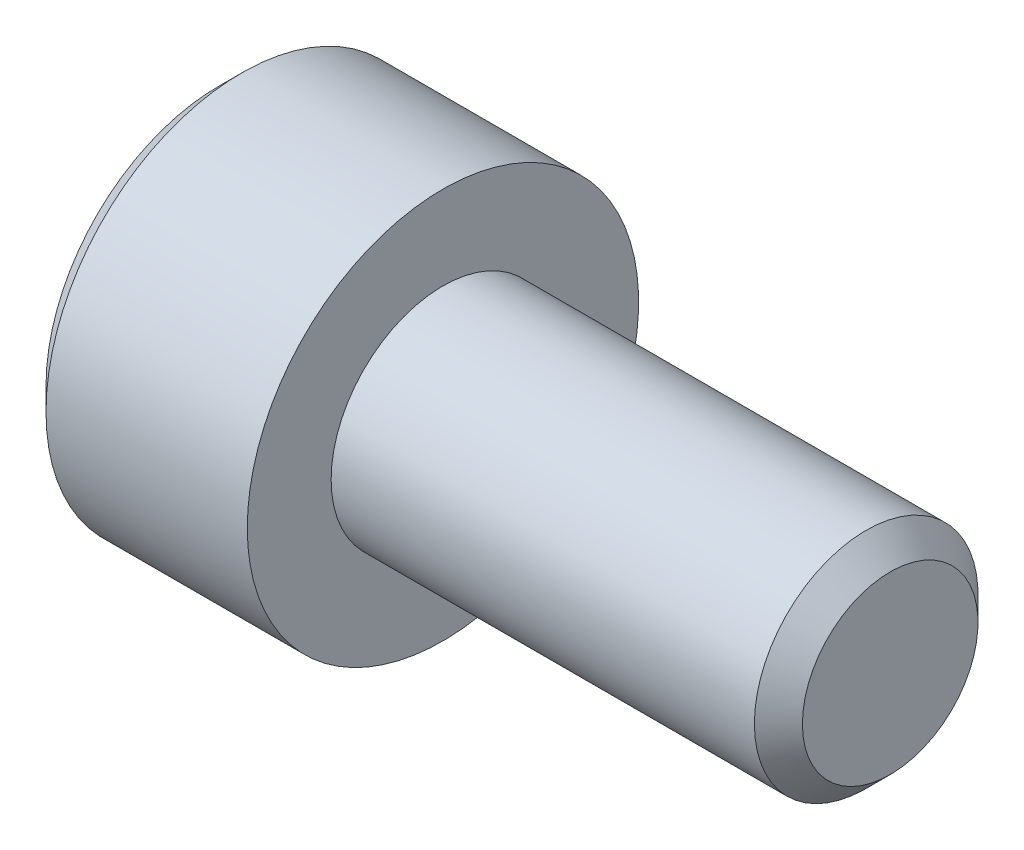
SolidWorks part; units mm, degrees
ref_plane "Front Plane" through (0, 0, 0) normal (0, 0, 1) x (1, 0, 0)
ref_plane "Top Plane" through (0, 0, 0) normal (0, 1, 0) x (1, 0, 0)
ref_plane "Right Plane" through (0, 0, 0) normal (1, 0, 0) x (0, 0, -1)
ref_plane "Plane1" through (1, 0, 0) normal (1, 0, 0) x (0, 0, -1)
ref_axis "Axis_X" through (-4.6, 0, 0) along (1, 0, 0)
ref_axis "Axis_Y" through (0, 3.85, 0) along (0, -1, 0)
ref_axis "Axis_Z" through (0, 0, -3.85) along (0, 0, 1)
sketch "Sketch1" plane through (0, 0, 0) normal (0, 0, 1) x (1, 0, 0)
  line L0 (-4, 0) -> (8, 0)
  line L1 (8, 0) -> (8, -1.5705)
  line L2 (8, -1.5705) -> (7.5705, -2)
  line L3 (7.5705, -2) -> (0, -2)
  line L4 (0, -2) -> (0, -3.5)
  line L5 (0, -3.5) -> (-3.6, -3.5)
  line L6 (-3.6, -3.5) -> (-4, -3.1)
  line L7 (-4, -3.1) -> (-4, 0)
  line L8 (0, 0) -> (-4, 0) construction
  line L9 (8, 1.5705) -> (7.5705, 2) construction
  line L10 (-4, 3.1) -> (-3.6, 3.5) construction
  point P16 (7.3, -2)
  dimension "A" = 7
  dimension "E" = 4
  dimension "MSM_1" = 3.141
  dimension "MSM_2" = 45
  dimension "MSM_3" = 0.4
  dimension "L" = 8
  dimension "Pitch_1" = 0.7
revolve "Revolve1" add sketch "Sketch1" angle 360 about axis through (-4.6, 0, 0) along (1, 0, 0)
sketch "Sketch2" plane through (-4, 0, 0) normal (-1, 0, 0) x (0, 0, 1)
  line L1 (0, 1.7321) -> (-1.5, 0.866)
  line L2 (-1.5, 0.866) -> (-1.5, -0.866)
  line L3 (-1.5, -0.866) -> (0, -1.7321)
  line L4 (0, -1.7321) -> (1.5, -0.866)
  line L5 (1.5, -0.866) -> (1.5, 0.866)
  line L6 (1.5, 0.866) -> (0, 1.7321)
  circle A0 centre (0, 0) radius 1.5 construction
  dimension "B" = 3
extrude "Cut-Extrude1" cut sketch "Sketch2" against normal blind 2
ref_plane "Dim. B_s" through (8, 0, 0) normal (1, 0, 0) x (0, 0, -1)
sketch "Sketch3" plane through (0, 0, 0) normal (0, 0, 1) x (1, 0, 0)
  line L0 (0, 0) -> (8, 0) construction
  line L1 (8, -1.3128) -> (8, 1.3128) construction
  line L3 (7.99, 2) -> (8, 2)
  line L5 (7.99, 2) -> (7.99, 1.99)
  line L6 (7.99, 1.99) -> (8, 1.99)
  line L7 (8, 2) -> (8, 1.99)
  line L8 (5, 2) -> (5.01, 2)
  line L9 (5, 2) -> (5, 1.99)
  line L10 (5, 1.99) -> (5.01, 1.99)
  line L11 (5.01, 2) -> (5.01, 1.99)
  dimension "MSM_5" = 0.01
  dimension "A_s" = 3
revolve "Cut-Revolve1" [suppressed] cut sketch "Sketch3" angle 360 about L0
equation "\"Factor\"= 1.082532"
equation "\"ATD_1\"= 4.134"
equation "\"L_s\"= 10"
equation "\"L_s\"= IIF ( ( \"M\" = 12 and \"L\" > 50 ) , 36 , IIF ( ( \"M\" = 10 and \"L\" > 40 ) , 32 , IIF ( ( \"M\" = 8 and \"L\" > 35 ) , 28 , IIF ( ( \"M\" = 6 and \"L\" > 30 ) , 24 , IIF ( ( \"M\" = 5 and \"L\" > 25 ) , 22 , IIF ( ( \"M\" = 4 and \"L\" > 25 ) , 20 , IIF ( ( \"M\" = 3 and \"L\" > 20 ) , 18 , \"L\" ) ) ) ) ) ) )"
equation "\"A\"= IIF ( \"M\" = 12 , 18 , IIF ( \"M\" = 10 , 16 , IIF ( \"M\" = 8 , 13 , IIF ( \"M\" = 6 , 10 , IIF ( \"M\" = 5 , 8.5 , IIF ( \"M\" = 4 , 7 , IIF ( \"M\" = 3 , 5.5 , IIF ( \"M\" = 2.6 or \"M\" = 2.5 , 4.5 , 3.8 ) ) ) ) ) ) ) )"
equation "\"E\"= \"M\""
equation "\"B\"= IIF ( \"M\" = 12 , 10 , IIF ( \"M\" = 10 , 8 , IIF ( \"M\" = 8 , 6 , IIF ( \"M\" = 6 , 5 , IIF ( \"M\" = 5 , 4 , IIF ( \"M\" = 4 , 3 , IIF ( \"M\" = 3 , 2.5 , IIF ( \"M\" = 2.6 or \"M\" = 2.5 , 2 , 1.5 ) ) ) ) ) ) ) )"
equation "\"MSM_4\"= \"M\" * 0.5"
equation "\"MSM_1\"= IIF ( \"M\" = 12 , 9.853 , IIF ( \"M\" = 10 , 8.16 , IIF ( \"M\" = 8 , 6.466 , IIF ( \"M\" = 6 , 4.773 , IIF ( \"M\" = 5 , 4.019 , IIF ( \"M\" = 4 , 3.141 , IIF ( \"M\" = 3 , 2.387 , IIF ( \"M\" = 2.6 , 2.048 , IIF ( \"M\" = 2.5 , 1.948 , 1.509 ) ) ) ) ) ) ) ) )"
equation "\"MSM_2\"= 45"
equation "\"MSM_3\"= IIF ( \"M\" = 2.6 , 0.26 , \"E\" * 0.1 )"
equation "\"Thread1\" = IIF ( ( ( \"M\" = 12 ) and ( \"L\" > 50 ) ) or ( ( \"M\" = 10 ) and ( \"L\" > 40 ) ) or ( ( \"M\" = 8 ) and ( \"L\" > 35 ) ) or ( ( \"M\" = 6 ) and ( \"L\" > 30 ) ) or ( ( \"M\" = 5 ) and ( \"L\" > 25 ) ) or ( ( \"M\" = 4 ) and ( \"L\" > 25 ) ) or ( \"M\" = 3 ) and ( \"L\" > 2 ) , \"suppressed\" , \"unsuppressed\" )"
equation "\"Thread2\" = IIF ( ( ( \"M\" = 12 ) and ( \"L\" > 50 ) ) or ( ( \"M\" = 10 ) and ( \"L\" > 40 ) ) or ( ( \"M\" = 8 ) and ( \"L\" > 35 ) ) or ( ( \"M\" = 6 ) and ( \"L\" > 30 ) ) or ( ( \"M\" = 5 ) and ( \"L\" > 25 ) ) or ( ( \"M\" = 4 ) and ( \"L\" > 25 ) ) or ( \"M\" = 3 ) and ( \"L\" > 2 ) , \"unsuppressed\" , \"suppressed\" )"
equation "\"MSM_5\"= 0.01"
equation "\"Cut-Revolve1\"= IIF ( \"TYP\" = 2 , \"unsuppressed\" , \"suppressed\" )"
equation "\"Pitch_1\"= IIF ( \"M\" = 12 , 1.75 , IIF ( \"M\" = 10 , 1.5 , IIF ( \"M\" = 8 , 1.25 , IIF ( \"M\" = 6 , 1 , IIF ( \"M\" = 5 , 0.8 , IIF ( \"M\" = 4 , 0.7 , IIF ( \"M\" = 3 , 0.5 , IIF ( \"M\" = 2.6 or \"M\" = 2.5 , 0.45 , 0.4 ) ) ) ) ) ) ) )"
equation "\"ATD_2\"= round ( \"M\" - \"Factor\" * \"Pitch_1\" , 3 )"
